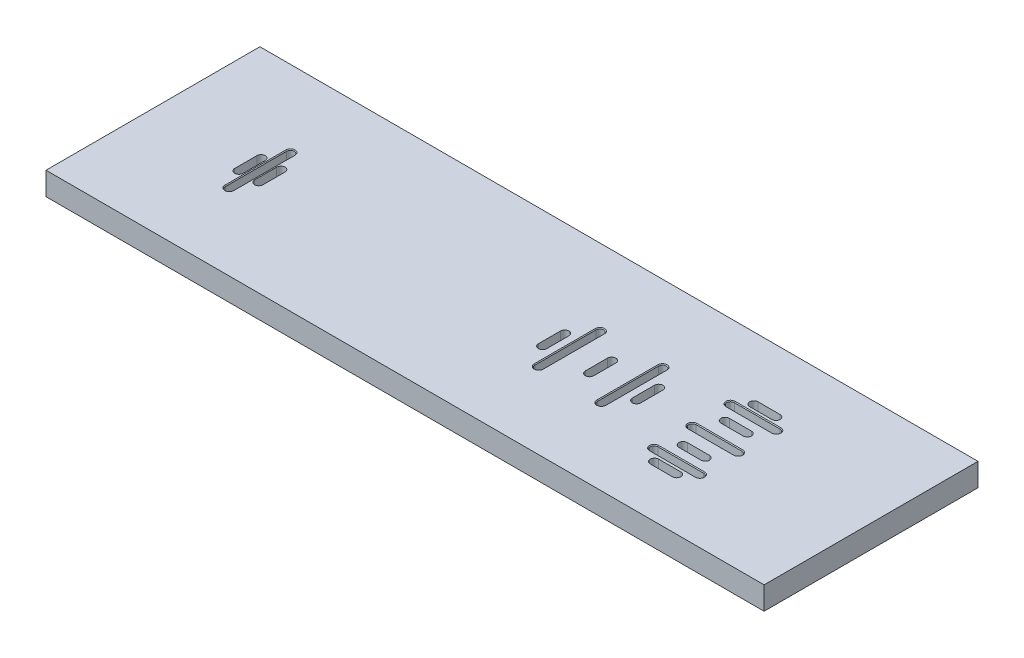
SolidWorks part; units mm, degrees
material "6061 Alloy"
ref_plane "Front Plane" through (0, 0, 0) normal (0, 0, 1) x (1, 0, 0)
ref_plane "Top Plane" through (0, 0, 0) normal (0, 1, 0) x (1, 0, 0)
ref_plane "Right Plane" through (0, 0, 0) normal (1, 0, 0) x (0, 0, -1)
sketch "Sketch1" plane through (0, 0, 0) normal (0, 1, 0) x (1, 0, 0)
  line L0 (10.5, 0) -> (264, 0) construction
  line L1 (286.5745, -3.5) -> (320.0389, -3.5) construction
  line L2 (223, 15) -> (223, -15) construction
  line L3 (286.5, -6) -> (316.5, -6)
  line L4 (286.5, -6) -> (286.5, -1) construction
  line L5 (286.5, -1) -> (316.5, -1)
  line L6 (182, 15) -> (182, -15) construction
  line L7 (264, 15) -> (264, -15) construction
  line L8 (-2.5, 20) -> (2.5, 20) construction
  line L9 (182, 15) -> (264, 15) construction
  line L10 (182, 15) -> (182, -15) construction
  line L11 (182, -15) -> (264, -15) construction
  line L12 (264, 15) -> (264, -15) construction
  line L13 (292.54, 34) -> (310.46, 34) construction
  line L14 (292.54, 34) -> (292.54, -41) construction
  line L15 (292.54, -41) -> (310.46, -41) construction
  line L16 (310.46, 34) -> (310.46, -41) construction
  line L17 (301.5, 34) -> (301.5, -41) construction
  line L18 (200, 20) -> (205, 20) construction
  line L19 (200, 20) -> (200, -20)
  line L20 (200, -20) -> (205, -20) construction
  line L21 (205, 20) -> (205, -20)
  line L22 (200, 20) -> (205, -20) construction
  line L23 (200, -20) -> (205, 20) construction
  line L24 (246, 20) -> (241, 20) construction
  line L25 (246, 20) -> (246, -20)
  line L26 (246, -20) -> (241, -20) construction
  line L27 (241, 20) -> (241, -20)
  line L28 (246, 20) -> (241, -20) construction
  line L29 (246, -20) -> (241, 20) construction
  line L30 (316.5, -6) -> (316.5, -1) construction
  line L31 (286.5, 19) -> (316.5, 19)
  line L32 (286.5, 19) -> (286.5, 24) construction
  line L33 (286.5, 24) -> (316.5, 24)
  line L34 (316.5, 19) -> (316.5, 24) construction
  line L35 (286.5, 19) -> (316.5, 24) construction
  line L36 (286.5, 24) -> (316.5, 19) construction
  line L37 (286.5, -31) -> (316.5, -31)
  line L38 (286.5, -31) -> (286.5, -26) construction
  line L39 (286.5, -26) -> (316.5, -26)
  line L40 (316.5, -31) -> (316.5, -26) construction
  line L41 (286.5, -31) -> (316.5, -26) construction
  line L42 (286.5, -26) -> (316.5, -31) construction
  line L43 (286.5, -6) -> (316.5, -1) construction
  line L44 (286.5, -1) -> (316.5, -6) construction
  line L45 (-2.5, 20) -> (-2.5, -20)
  line L46 (10.5, 15) -> (-10.5, 15) construction
  line L47 (10.5, 15) -> (10.5, -15) construction
  line L48 (10.5, -15) -> (-10.5, -15) construction
  line L49 (-10.5, 15) -> (-10.5, -15) construction
  line L50 (-2.5, -20) -> (2.5, -20) construction
  line L51 (2.5, 20) -> (2.5, -20)
  line L52 (-2.5, 20) -> (2.5, -20) construction
  line L53 (-2.5, -20) -> (2.5, 20) construction
  line L54 (-10.5, 0) -> (10.5, 0) construction
  arc A0 (200, 20) -> (205, 20) centre (202.5, 20) cw
  arc A1 (241, 20) -> (246, 20) centre (243.5, 20) cw
  arc A2 (241, -20) -> (246, -20) centre (243.5, -20) ccw
  arc A3 (200, -20) -> (205, -20) centre (202.5, -20) ccw
  arc A4 (316.5, 24) -> (316.5, 19) centre (316.5, 21.5) cw
  arc A5 (286.5, 19) -> (286.5, 24) centre (286.5, 21.5) cw
  arc A6 (286.5, -31) -> (286.5, -26) centre (286.5, -28.5) cw
  arc A7 (316.5, -26) -> (316.5, -31) centre (316.5, -28.5) cw
  arc A8 (316.5, -1) -> (316.5, -6) centre (316.5, -3.5) cw
  arc A9 (286.5, -6) -> (286.5, -1) centre (286.5, -3.5) cw
  arc A10 (-2.5, 20) -> (2.5, 20) centre (0, 20) cw
  arc A11 (-2.5, -20) -> (2.5, -20) centre (0, -20) ccw
  point P2 (0, 0)
  point P3 (0, 0)
  point P9 (301.5, -3.5)
  point P10 (301.5, -3.5)
  point P11 (182, 0)
  point P14 (264, 0)
  point P21 (292.54, -3.5)
  point P22 (310.46, -3.5)
  point P28 (223, 15)
  point P29 (223, -15)
  point P32 (202.5, 0)
  point P33 (243.5, 0)
  point P34 (223, 0)
  point P35 (202.5, 0)
  point P40 (243.5, 0)
  point P51 (301.5, -3.5)
  point P52 (301.5, -28.5)
  point P53 (301.5, 21.5)
  point P54 (301.5, 21.5)
  point P59 (301.5, -28.5)
  dimension "D2" = 82
  dimension "D3" = 28.54
  dimension "D4" = 17.92
  dimension "D5" = 171.5
  dimension "D6" = 20.5
  dimension "D7" = 20.5
  dimension "D8" = 25
  dimension "D9" = 25
  dimension "D10" = 26
  dimension "D11" = 21
  dimension "D12" = 75
  dimension "D13" = 30
  dimension "D14" = 30
sketch "Sketch2" plane through (0, 0, 0) normal (0, 1, 0) x (1, 0, 0)
  line L0 (-70, 0) -> (482.4634, 0) construction
  line L1 (-70, 70) -> (400, 70)
  line L2 (-70, 70) -> (-70, -70)
  line L3 (-70, -70) -> (400, -70)
  line L4 (400, 70) -> (400, -70)
extrude "Boss-Extrude1" add sketch "Sketch2" against normal blind 15
extrude "Cut-Extrude1" cut sketch "Sketch1" against normal blind 7.5
chamfer "Chamfer1" distance 0.5 angle 45 24 edges at (301.5, 0, 31) (319, 0, 28.5) (284, 0, 28.5) (301.5, 0, 26) (301.5, 0, -19) (319, 0, -21.5) (284, 0, -21.5) (301.5, 0, -24) (241, 0, 0) (243.5, 0, 22.5) (243.5, 0, -22.5) (246, 0, 0) (200, 0, 0) (202.5, 0, 22.5) (202.5, 0, -22.5) (205, 0, 0) (-2.5, 0, 0) (0, 0, 22.5) (0, 0, -22.5) (2.5, 0, 0) (301.5, 0, 6) (319, 0, 3.5) (284, 0, 3.5) (301.5, 0, 1)
sketch "Sketch3" plane through (0, -15, 0) normal (0, 1, 0) x (1, 0, 0)
  line L0 (10.5, 0) -> (264, 0) construction
  line L1 (301.5, 34) -> (301.5, -41) construction
  line L2 (-10.5, 0) -> (10.5, 0) construction
  point P0 (223, 0)
  point P1 (253.75, 0)
  point P3 (192.25, 0)
  point P6 (301.5, -3.5)
  point P7 (301.5, 10.25)
  point P10 (301.5, -17.25)
  point P12 (301.5, 29)
  point P13 (301.5, -36)
  point P14 (-6.5, 0)
  point P15 (6.5, 0)
  dimension "D1" = 30.75
  dimension "D2" = 30.75
  dimension "D3" = 13.75
  dimension "D4" = 13.75
  dimension "D5" = 18.75
  dimension "D6" = 18.75
  dimension "D7" = 6.5
  dimension "D8" = 6.5
hole_wizard "CSK SLOT for M5 SFHCS2" positions "Sketch8" profile "Sketch7" size "M5" standard "ANSI Metric" slot yes end condition through all
sketch "Sketch8" plane through (0, -15, 0) normal (0, -1, 0) x (-1, 0, 0)
  line L0 (-291.5, 10.25) -> (-311.5, 10.25) construction
  point P0 (-301.5, 10.25)
  point P5 (-301.5, -17.25)
  point P8 (-301.5, -36)
  point P17 (-301.5, 29)
  dimension "D1" = 20
sketch "Sketch7" plane through (301.5, -15, -10.25) normal (1, 0, 0) x (0, 0, -1)
  line L0 (0, 0) -> (0, 15)
  line L1 (0, 15) -> (2.75, 15)
  line L2 (2.75, 15) -> (2.75, 2.85)
  line L3 (2.75, 2.85) -> (5.6, 0)
  line L5 (5.6, 0) -> (0, 0)
  line L6 (-2.75, 2.85) -> (-5.6, 0) construction
  line L11 (0, -6.35) -> (0, 107.95) construction
  dimension "Thru Hole Dia." = 5.5
  dimension "Thru Hole Depth" = 15
  dimension "Near C'Sink Dia." = 11.2
  dimension "Near C'Sink Angle" = 90
hole_wizard "CSK SLOT for M5 SFHCS1" positions "Sketch10" profile "Sketch9" size "M5" standard "ANSI Metric" slot yes end condition through all
sketch "Sketch10" plane through (0, -15, 0) normal (0, -1, 0) x (-1, 0, 0)
  line L0 (-253.75, -10) -> (-253.75, 10) construction
  point P0 (-253.75, 0)
  point P8 (-223, 0)
  point P11 (-192.25, 0)
  point P14 (-6.5, 0)
  point P17 (6.5, 0)
  dimension "D1" = 20
sketch "Sketch9" plane through (253.75, -15, 0) normal (1, 0, 0) x (0, 0, -1)
  line L0 (0, 0) -> (0, 15)
  line L1 (0, 15) -> (2.75, 15)
  line L2 (2.75, 15) -> (2.75, 2.85)
  line L3 (2.75, 2.85) -> (5.6, 0)
  line L5 (5.6, 0) -> (0, 0)
  line L6 (-2.75, 2.85) -> (-5.6, 0) construction
  line L11 (0, -6.35) -> (0, 107.95) construction
  dimension "Thru Hole Dia." = 5.5
  dimension "Thru Hole Depth" = 15
  dimension "Near C'Sink Dia." = 11.2
  dimension "Near C'Sink Angle" = 90
